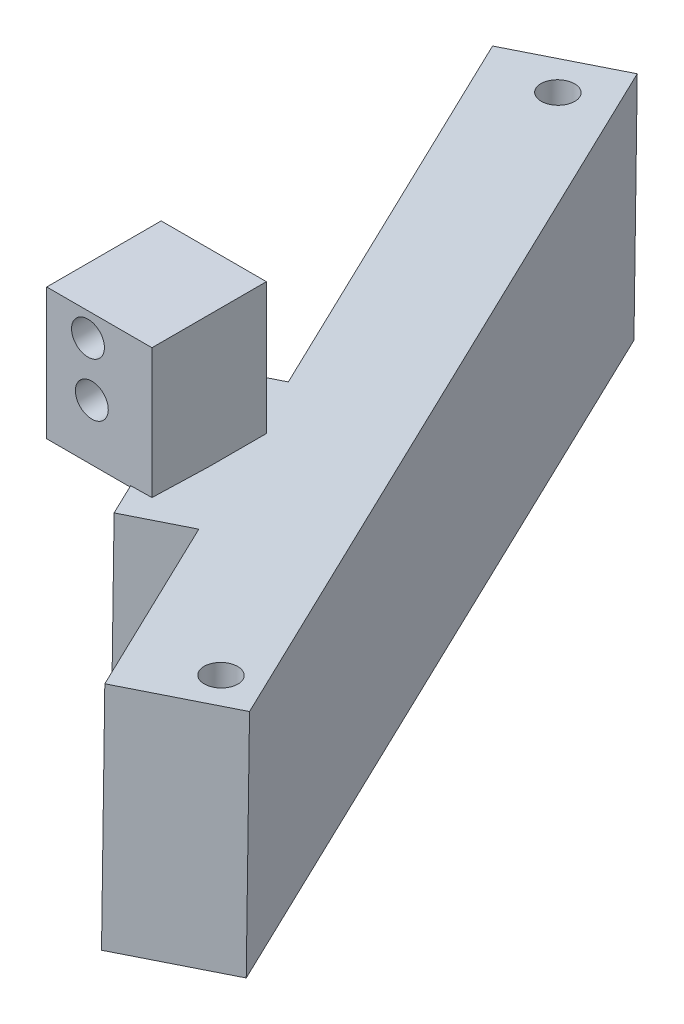
SolidWorks part; units mm, degrees
ref_plane "Front Plane" through (0, 0, 0) normal (0, 0, 1) x (1, 0, 0)
ref_plane "Top Plane" through (0, 0, 0) normal (0, 1, 0) x (1, 0, 0)
ref_plane "Right Plane" through (0, 0, 0) normal (1, 0, 0) x (0, 0, -1)
sketch "Sketch2" plane through (0, 0, 0) normal (0, 0, 1) x (1, 0, 0)
  line L0 (-194.337, 238.2488) -> (-194.337, 212.8488)
  line L1 (-194.337, 212.8488) -> (-174.017, 212.8488)
  line L2 (-174.017, 212.8488) -> (-174.017, 238.2488)
  line L3 (-174.017, 238.2488) -> (-194.337, 238.2488)
  circle A0 centre (-186.3724, 233.6772) radius 3.175
  circle A1 centre (-185.6285, 223.6772) radius 3.175
  dimension "D6" = 6.35
  dimension "D7" = 6.35
  dimension "D1" = 90
  dimension "D2" = 5.08
  dimension "D3" = 20.32
  dimension "D4" = 25.4
  dimension "D5" = 3.175
extrude "Boss-Extrude1" add sketch "Sketch2" along normal up to surface (22.098 mm away)
ref_plane "Plane1" through (-3.3927, 215.0063, -6.5391) normal (-0.0158, 0.9994, -0.0304) x (0.9999, 0.0158, -0.0005)
sketch "Sketch3" plane through (-3.3927, 215.0063, -6.5391) normal (-0.0158, 0.9994, -0.0304) x (0.9999, 0.0158, -0.0005)
  line L7 (-217.4516, 84.0765) -> (-198.8235, 93.3905)
  line L8 (-198.8235, 93.3905) -> (-123.8526, -56.5512)
  line L9 (-123.8526, -56.5512) -> (-142.4817, -65.8658)
  line L10 (-142.4817, -65.8658) -> (-160.6576, -29.5142)
  line L11 (-160.6576, -29.5142) -> (-171.5624, -34.9666)
  line L12 (-171.5624, -34.9666) -> (-188.869, -0.3535)
  line L13 (-188.869, -0.3535) -> (-177.9631, 5.0994)
  line L14 (-177.9631, 5.0994) -> (-217.4516, 84.0765)
  circle A0 centre (-132.9342, -52.9758) radius 3.175
  circle A1 centre (-203.0882, 82.3172) radius 3.175
  circle A2 centre (-132.9342, -52.9758) radius 3.175 construction
  circle A3 centre (-203.0882, 82.3172) radius 3.175 construction
  dimension "D6" = 5.3241
  dimension "D10" = 6.35
  dimension "D11" = 6.35
  dimension "D2" = 20.828
  dimension "D3" = 20.8268
  dimension "D4" = 33.02
  dimension "D5" = 45.115
  dimension "D7" = 167.64
  dimension "D8" = 38.6986
  dimension "D9" = 88.299
  dimension "D12" = 7.2594
extrude "Boss-Extrude2" add sketch "Sketch3" against normal up to surface (43.583 mm away)
